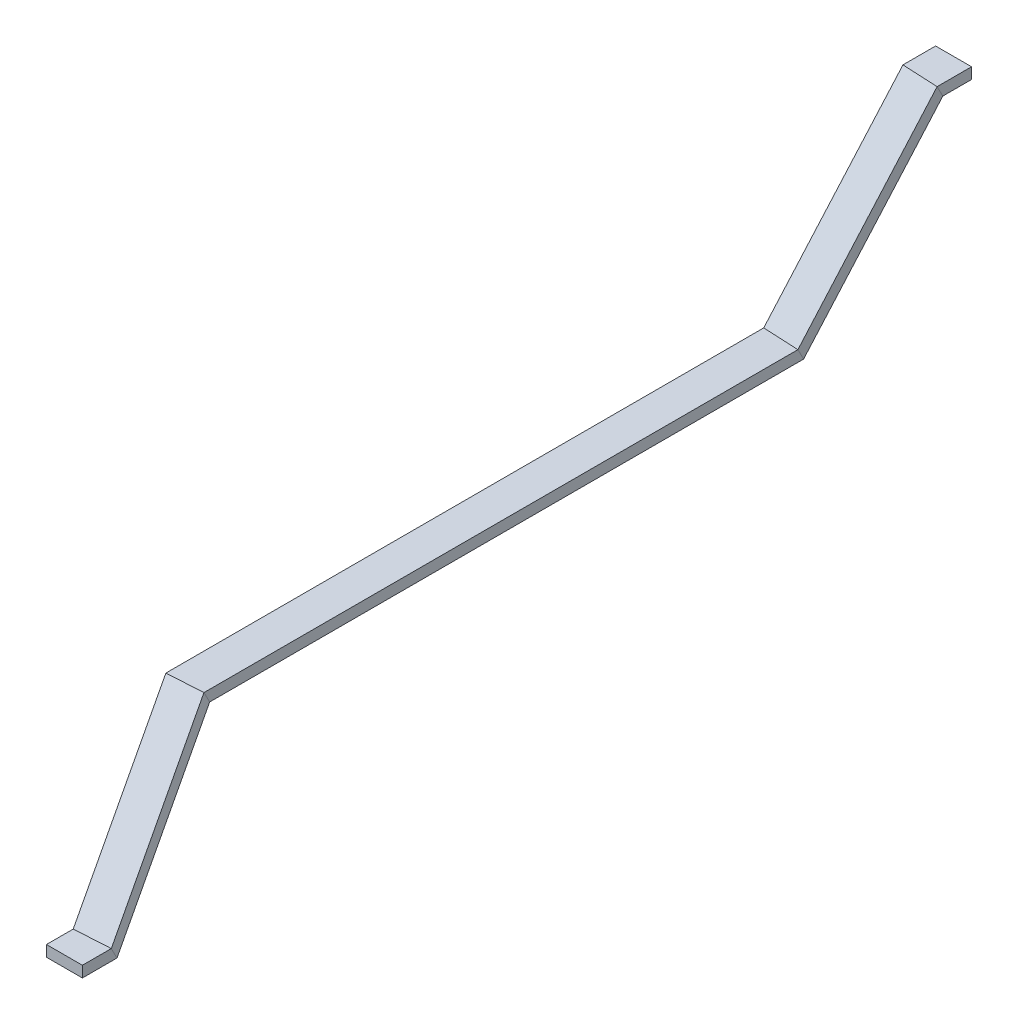
SolidWorks part; units mm, degrees
ref_plane "Front Plane" through (0, 0, 0) normal (0, 0, 1) x (1, 0, 0)
ref_plane "Top Plane" through (0, 0, 0) normal (0, 1, 0) x (1, 0, 0)
ref_plane "Right Plane" through (0, 0, 0) normal (1, 0, 0) x (0, 0, -1)
sketch3d "3DSketch1"
  line L0 (3251.1818, -307.3272, 1441.6243) -> (3251.1818, -307.3272, 1381.6243)
  line L1 (3215.675, 0, 1165) -> (3251.1818, -307.3272, 1381.6243)
  line L2 (3215.675, 0, 0) -> (3247.7853, 341.356, -240.0752)
  line L3 (3215.675, 0, 1165) -> (3215.675, 0, 0)
  line L6 (3247.7853, 341.356, -240.0752) -> (3247.7853, 341.356, -300.0752)
  point P0 (3215.675, 0, 0)
  point P2 (3247.7853, 341.356, -300.0752)
  point P3 (3215.675, 0, 1165)
  point P12 (3251.1818, -307.3272, 1381.6243)
  point P15 (3247.7853, 341.356, -240.0752)
  point P21 (3251.1818, -307.3272, 1441.6243)
  dimension "D1" = 1165
  dimension "D5" = 3251.1818
  dimension "D6" = 307.3272
  dimension "D8" = 60
  dimension "D12" = 3247.7853
  dimension "D13" = 341.356
  dimension "D15" = 60
  dimension "D2" = 125
  dimension "D3" = 125
ref_plane "Plane2" through (3247.7853, 341.356, -300.0752) normal (0, 0, 1) x (1, 0, 0)
sketch "Sketch2" plane through (3247.7853, 341.356, -300.0752) normal (0, 0, 1) x (1, 0, 0)
  line L1 (-35.125, 10.8) -> (35.125, 10.8)
  line L2 (-35.125, 10.8) -> (-35.125, -10.8)
  line L3 (-35.125, -10.8) -> (35.125, -10.8)
  line L4 (35.125, 10.8) -> (35.125, -10.8)
  point P4 (35.125, 0)
  point P5 (0, 10.8)
  dimension "D1" = 21.6
  dimension "D2" = 70.25
sweep "Sweep1" add profiles "Sketch2" path "3DSketch1"
equation "\"axialLength\"= 925mm"
equation "\"lengthAfterAxial\"= 240mm"
equation "\"Di\"= 6197.6mm'stator inner diameter"
equation "\"wedgeHeight\"= 4mm"
equation "\"spacerHeight\"= 7.5mm"
equation "\"coilHeight\"= 70.25mm'with isolation"
equation "\"coilWidth\"= 21.6mm'with isolation"
equation "\"r1\"= \"Di\" / 2 + \"wedgeHeight\" + \"spacerHeight\" + \"coilHeight\" * 3 / 2 + 50mm"
equation "\"theta1\"= 1deg"
equation "\"z1\"= \"axialLength\" + \"lengthAfterAxial\" + 50mm"
equation "\"D1@3DSketch1\"= \"axialLength\" + \"lengthAfterAxial\""
equation "\"r2\"= \"r1\""
equation "\"theta2\"= 4.5 * 1.2deg"
equation "\"z2\"= \"z1\" + 200mm"
equation "\"D5@3DSketch1\"= \"r2\" * cos ( \"theta2\" )"
equation "\"D6@3DSketch1\"= \"r2\" * sin ( \"theta2\" )"
equation "\"connectionHeight\"= 120mm'height of the joint part"
equation "\"r3\"= \"r1\""
equation "\"theta3\"= 1deg"
equation "\"z3\"= 50mm"
equation "\"r4\"= \"r3\""
equation "\"theta4\"= 1.2 * 5deg"
equation "\"z4\"= \"z3\" + 200mm"
equation "\"D12@3DSketch1\"= \"r4\" * cos ( \"theta4\" )"
equation "\"D13@3DSketch1\"= \"r4\" * sin ( \"theta4\" )"
equation "\"D15@3DSketch1\"= \"connectionHeight\" / 2"
equation "\"fillet\"= 30mm"
equation "\"D1@Sketch2\"= \"coilWidth\""
equation "\"D2@Sketch2\"= \"coilHeight\""
equation "\"endWindingAngle\"= 125deg"
equation "\"D2@3DSketch1\"= \"endWindingAngle\""
equation "\"D3@3DSketch1\"= \"endWindingAngle\""
